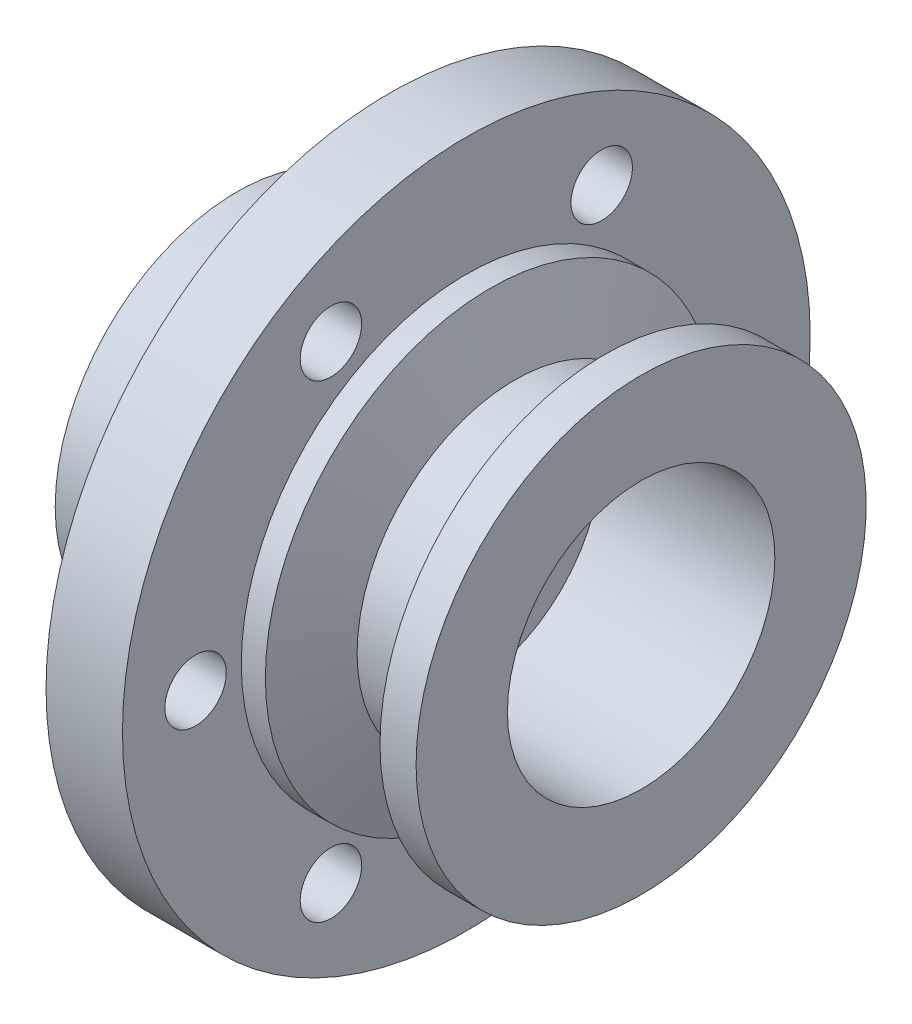
SolidWorks part; units mm, degrees
ref_plane "Front" through (0, 0, 0) normal (0, 0, 1) x (1, 0, 0)
ref_plane "Top" through (0, 0, 0) normal (0, 1, 0) x (1, 0, 0)
ref_plane "Right" through (0, 0, 0) normal (1, 0, 0) x (0, 0, -1)
sketch "Sketch1" plane through (0, 0, 0) normal (0, 0, 1) x (1, 0, 0)
  line L0 (-12.7, 15.1125) -> (0, 15.1125)
  line L1 (0, 15.1125) -> (0, 28.575)
  line L2 (0, 28.575) -> (6.35, 28.575)
  line L3 (6.35, 28.575) -> (6.35, 18.7005)
  line L4 (6.35, 18.7005) -> (8.35, 18.7005)
  line L5 (8.35, 18.7005) -> (10.3839, 13.1125)
  line L6 (10.3839, 13.1125) -> (15.8411, 13.1125)
  line L7 (15.8411, 13.1125) -> (17.875, 18.7005)
  line L8 (17.875, 18.7005) -> (20.875, 18.7005)
  line L9 (20.875, 18.7005) -> (20.875, 11.1125)
  line L10 (0, 0) -> (27.6559, 0) construction
  line L12 (20.875, 11.1125) -> (6.4125, 11.1125)
  line L13 (6.4125, 11.1125) -> (6.4125, 8.9375)
  line L14 (6.4125, 8.9375) -> (1.5875, 8.9375)
  line L15 (1.5875, 8.9375) -> (1.5875, 11.1125)
  line L16 (1.5875, 11.1125) -> (-12.7, 11.1125)
  line L17 (-12.7, 11.1125) -> (-12.7, 15.1125)
  line L18 (13.1125, 13.1125) -> (13.1125, 25.8182) construction
  dimension "D1" = 9.525
  dimension "D3" = 30.225
  dimension "D4" = 22.225
  dimension "D5" = 5.588
  dimension "D7" = 2
  dimension "D8" = 40
  dimension "D9" = 14.2875
  dimension "D10" = 14.4625
  dimension "D11" = 3
  dimension "D12" = 2
  dimension "D13" = 6.35
  dimension "D14" = 17.875
  dimension "D15" = 12.7
  dimension "D16" = 57.15
revolve "Revolve1" add sketch "Sketch1" angle 360 about L10
hole_wizard "1/4-20 Tapped Hole1" positions "Sketch2" profile "Sketch4" tap size "1/4-20" standard "ANSI Inch"
sketch "Sketch2" plane through (0, 0, 0) normal (-1, 0, 0) x (0, 0, 1)
  circle A0 centre (0, 0) radius 22.5 construction
  point P16 (-22.5, 0)
  point P24 (-11.25, 19.4856)
  point P25 (11.25, 19.4856)
  point P26 (22.5, 0)
  point P27 (11.25, -19.4856)
  point P28 (-11.25, -19.4856)
  dimension "D1" = 45
  dimension "D2" = 6
sketch "Sketch4" plane through (0, -19.4856, -11.25) normal (0, 1, 0) x (0, 0, 1)
  line L0 (0, 0) -> (0, 18.0438)
  line L1 (0, 18.0438) -> (2.5527, 16.51)
  line L2 (2.5527, 16.51) -> (2.5527, 0)
  line L5 (2.5527, 0) -> (0, 0)
  line L10 (0, 18.0438) -> (-2.5527, 16.51) construction
  line L11 (0, -6.35) -> (0, 107.95) construction
  dimension "Tap Drill Dia." = 5.1054
  dimension "Tap Drill Depth" = 16.51
  dimension "Drill Angle" = 118
cosmetic thread "Hole Thread1"
cosmetic thread "Hole Thread2"
cosmetic thread "Hole Thread3"
cosmetic thread "Hole Thread4"
cosmetic thread "Hole Thread7"
cosmetic thread "Hole Thread8"
